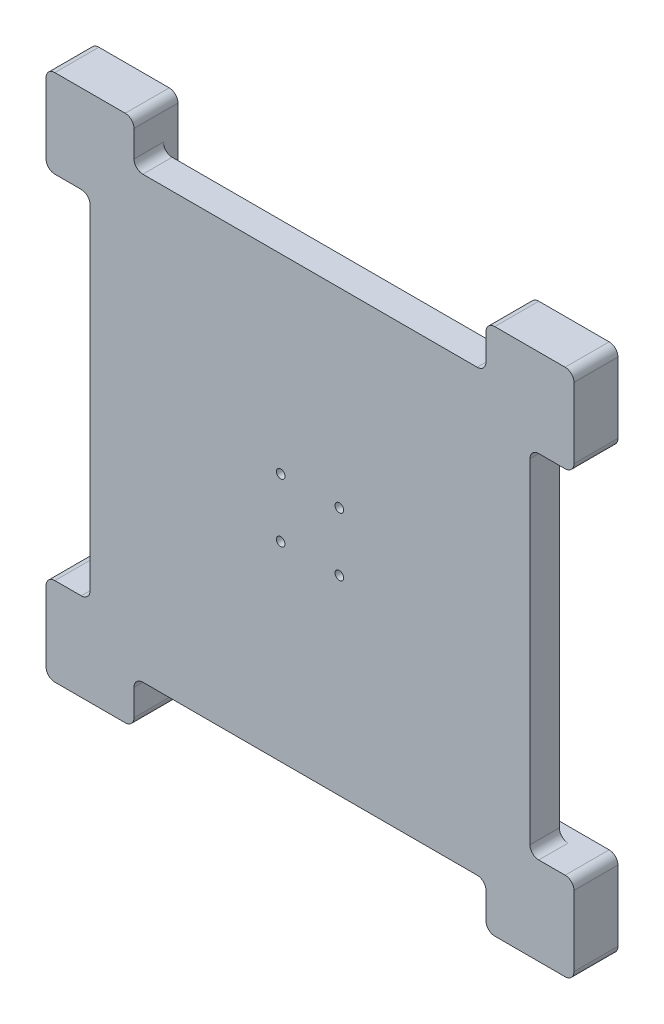
SolidWorks part; units mm, degrees
ref_plane "Front Plane" through (0, 0, 0) normal (0, 0, 1) x (1, 0, 0)
ref_plane "Top Plane" through (0, 0, 0) normal (0, 1, 0) x (1, 0, 0)
ref_plane "Right Plane" through (0, 0, 0) normal (1, 0, 0) x (0, 0, -1)
sketch "Sketch1" plane through (0, 0, 0) normal (0, 0, 1) x (1, 0, 0)
  line L1 (75, 75) -> (-75, 75)
  line L2 (75, 75) -> (75, -75)
  line L3 (75, -75) -> (-75, -75)
  line L4 (-75, 75) -> (-75, -75)
  line L5 (75, 75) -> (-75, -75) construction
  line L6 (75, -75) -> (-75, 75) construction
  point P0 (0, 0)
  dimension "D1" = 150
  dimension "D2" = 150
extrude "Boss-Extrude1" add sketch "Sketch1" along normal blind 10
sketch "Sketch2" plane through (0, 0, 10) normal (0, 0, 1) x (1, 0, 0)
  line L1 (60, -60) -> (90, -60)
  line L2 (60, -60) -> (60, -90)
  line L3 (60, -90) -> (90, -90)
  line L4 (90, -60) -> (90, -90)
  line L5 (60, -60) -> (90, -90) construction
  line L6 (60, -90) -> (90, -60) construction
  point P0 (75, -75)
  dimension "D1" = 30
extrude "Boss-Extrude2" add sketch "Sketch2" against normal blind 15
mirror "Mirror1" about plane through (0, 0, 0) normal (0, 1, 0) of "Boss-Extrude2"
mirror "Mirror2" about plane through (0, 0, 0) normal (1, 0, 0) of "Mirror1"
fillet "Fillet1" radius 3 20 edges at (-75, 60, 5) (-90, 60, 2.5) (-90, 90, 2.5) (-60, 90, 2.5) (-60, 75, 5) (60, 75, 5) (60, 90, 2.5) (90, 90, 2.5) (90, 60, 2.5) (75, 60, 5) (75, -60, 5) (90, -60, 2.5) (90, -90, 2.5) (60, -90, 2.5) (60, -75, 5) (-60, -90, 2.5) (-90, -90, 2.5) (-90, -60, 2.5) (-75, -60, 5) (-60, -75, 5)
sketch "Sketch4" plane through (0, 0, 10) normal (0, 0, 1) x (1, 0, 0)
  line L0 (-57, -75) -> (57, -75) construction
  line L1 (0, 0) -> (0, -75) construction
  circle A0 centre (10, -10) radius 1.47
  dimension "D1" = 2.94
  dimension "D2" = 10
  dimension "D4" = 10
extrude "Cut-Extrude2" cut sketch "Sketch4" against normal blind 10
mirror "Mirror3" about plane through (0, 0, 0) normal (1, 0, 0) of "Cut-Extrude2"
mirror "Mirror4" about plane through (0, 0, 0) normal (0, 1, 0) of "Mirror3"
ref_axis "Axis1" through (0, 0, -5.75) along (0, 0, 1)
